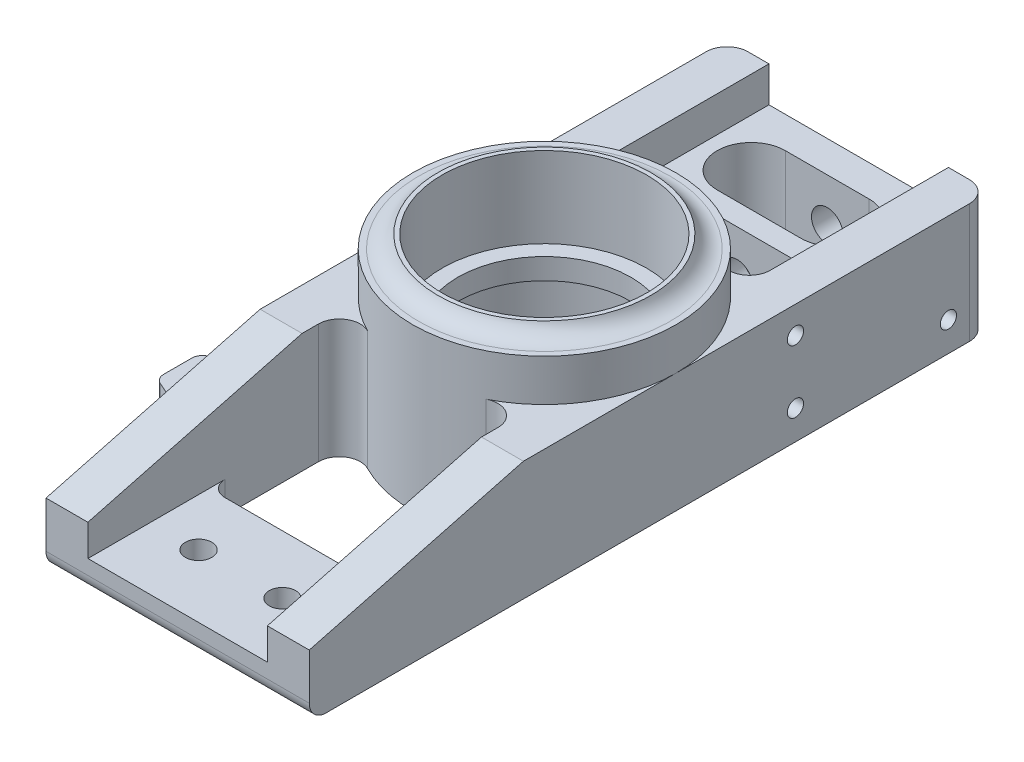
SolidWorks part; units mm, degrees
material "6061-T6 (SS)"
ref_plane "X-Y Datum" through (0, 0, 0) normal (0, 0, 1) x (1, 0, 0)
ref_plane "X-Z Datum" through (0, 0, 0) normal (0, 1, 0) x (1, 0, 0)
ref_plane "Y-Z Datum" through (0, 0, 0) normal (1, 0, 0) x (0, 0, -1)
sketch3d "KPI Sketch"
  line L0 (0, 0, 0) -> (0, 0, 50000) construction
  line L1 (0, 0, 0) -> (0, -50000, 0) construction
  line L2 (0, 0, 0) -> (-50000, 0, 0) construction
  line L3 (0, 15.9209, 92.075) -> (0, -42.747, -247.2184) construction
  line L4 (0, -10.9799, -63.5) -> (-66.3575, -10.9799, -63.5) construction
  line L5 (-66.3575, -10.9799, -63.5) -> (-66.3575, -0.8199, -63.5) construction
  line L6 (-66.3575, -0.8199, -63.5) -> (0, -10.9799, -63.5) construction
  line L7 (-66.3575, -0.8199, -52.3875) -> (-66.3575, -0.8199, -74.6125) construction
  line L8 (0, 15.9209, 92.075) -> (0, 15.9209, -75.3861) construction
  line L9 (0, -13.0351, -75.3861) -> (0, 15.9209, -75.3861) construction
  line L10 (0, -10.9799, -63.5) -> (66.3575, -10.9799, -63.5) construction
  line L11 (66.3575, -10.9799, -63.5) -> (66.3575, -0.8199, -63.5) construction
  line L12 (66.3575, -0.8199, -63.5) -> (0, -10.9799, -63.5) construction
  line L13 (66.3575, -0.8199, -63.5) -> (66.3575, -0.8199, -52.3875) construction
  line L16 (66.3575, -0.8199, -63.5) -> (66.3575, -0.8199, -74.6125) construction
  circle A0 centre (0, 0, 0) radius 127 construction
  point P11 (0, -13.0351, -75.3861)
  point P17 (-66.3575, -0.8199, -63.5)
  point P18 (0, 0, 0)
  point P19 (-66.3575, -0.8199, -63.5)
  point P22 (0, 127, 0)
  dimension "D5" = 92.075
  dimension "D8" = 254
  dimension "TOE Z" = 63.5
  dimension "D1" = 10.16
  dimension "D4" = 67.1308
  dimension "D6" = 22.225
  dimension "D2" = 169.9461
  dimension "D3" = 28.956
  dimension "D7" = 66.3575
  dimension "D9" = 66.3575
  dimension "D10" = 10.16
  dimension "D11" = 11.1125
  dimension "D12" = 11.1125
ref_axis "Wheel Spin Axis" through (0, -55.5512, 0) along (0, 1, 0)
sketch "Bearing Sketch" plane through (0, 0, 0) normal (1, 0, 0) x (0, 0, -1)
  line L11 (0, 0) -> (0, -50000) construction
  line L17 (-30.9994, -25.0922) -> (-39.8894, -25.0922)
  line L23 (-30.9994, -3.175) -> (-26.2369, -3.175)
  line L24 (55.1739, 0) -> (-55.1739, 0) construction
  line L26 (-30.9994, -3.175) -> (-30.9994, -25.0922)
  line L27 (-30.9994, 27.6332) -> (-30.9994, 3.175)
  line L28 (-30.9994, 3.175) -> (-26.2369, 3.175)
  line L29 (-26.2369, 3.175) -> (-26.2369, -3.175)
  line L31 (0, 0) -> (-50000, 0) construction
  line L33 (-30.9994, 27.6332) -> (-32.2694, 27.6332)
  line L34 (-32.2694, 27.6332) -> (-32.2694, 23.7622)
  line L35 (-32.2694, 23.7622) -> (-39.8894, 23.7622)
  line L36 (-39.8894, 23.7622) -> (-39.8894, -25.0922)
  point P3 (-26.2369, 0)
  dimension "D2" = 6.35
  dimension "D1" = 21.9172
  dimension "D4" = 24.4582
  dimension "D3" = 52.4739
  dimension "D6" = 61.9989
  dimension "D5" = 79.7789
  dimension "D7" = 64.5389
  dimension "D8" = 48.8544
revolve "Bearing Dimensions" add sketch "Bearing Sketch" angle 360 about axis through (0, -55.5512, 0) along (0, 1, 0)
sketch "UBJ Material Sketch" plane through (0, -25.0922, 0) normal (0, 1, 0) x (1, 0, 0)
  line L1 (39.8894, -46.2394) -> (-39.8894, -46.2394)
  line L3 (0, 0) -> (-50000, 0) construction
  line L4 (0, 0) -> (0, -50000) construction
  line L5 (39.8894, 0) -> (39.8894, -46.2394)
  line L7 (-39.8894, 0) -> (-39.8894, -46.2394)
  circle A0 centre (0, 0) radius 39.8894 construction
  circle A1 centre (0, 0) radius 39.8894 construction
  arc A2 (-39.8894, 0) -> (39.8894, 0) centre (0, 0) ccw
  point P5 (0, -46.2394)
  point P15 (0, -39.8894)
  dimension "D1" = 6.35
extrude "UBJ Material" add sketch "UBJ Material Sketch" along normal offset from surface (36.1544 mm away) 12.7 up to face at (0, 23.7622, -39.8894)
sketch "Sketch58" plane through (39.8894, 0, 0) normal (1, 0, 0) x (0, 0, -1)
  line L0 (0, 0) -> (-50000, 0) construction
  line L5 (0, 0) -> (0, 50000) construction
  line L14 (-46.2394, 11.0622) -> (-111.125, -6.0422)
  line L16 (-111.125, -6.0422) -> (-111.125, -25.0922)
  line L17 (-111.125, -25.0922) -> (-62.9981, -25.0922)
  line L18 (-62.9981, -25.0922) -> (-46.2394, -25.0922)
  line L19 (-46.2394, -25.0922) -> (-46.2394, 11.0622)
  line L22 (-46.2394, -25.0922) -> (0, -25.0922) construction
  point P27 (-111.125, -15.5672)
  dimension "D1" = 19.05
  dimension "D2" = 64.8856
extrude "Boss-Extrude6" add sketch "Sketch58" against normal up to surface (79.7789 mm away) contours L16 L17 L18 L19 L14 up to face at (-39.8894, -7.015, 23.1197)
sketch "Sketch9" plane through (0, -25.0922, 0) normal (0, -1, 0) x (1, 0, 0)
  line L3 (-39.8894, 0) -> (-39.8894, 111.125) construction
  line L4 (-39.8894, 0) -> (-39.8894, 111.125) construction
  line L5 (0, 0) -> (-50000, 0) construction
  line L7 (-27.1894, 29.1874) -> (-27.1894, 74.3672)
  line L12 (27.1894, 74.3672) -> (-27.1894, 74.3672)
  line L13 (27.1894, 74.3672) -> (27.1894, 29.1874)
  line L17 (39.8894, 111.125) -> (39.8894, 0) construction
  line L21 (39.8894, 111.125) -> (39.8894, 0) construction
  arc A2 (39.8894, 0) -> (-39.8894, 0) centre (0, 0) ccw construction
  arc A3 (27.1894, 29.1874) -> (-27.1894, 29.1874) centre (0, 0) ccw
  dimension "D1" = 12.7
  dimension "D2" = 12.7
extrude "UBJ Cross Member" cut sketch "Sketch9" against normal through all contours A3 L13 L12 L7 region at (0, -25.0922, 55.3249)
ref_plane "Plane1" through (0, 3.6475, 0) normal (0, -1, 0) x (-1, 0, 0)
sketch "Sketch10" plane through (0, 3.6475, -1.6553) normal (0, 1, 0) x (1, 0, 0)
  line L9 (27.1894, -70.1197) -> (-27.1894, -70.1197)
  line L10 (27.1894, -70.1197) -> (27.1894, -114.5697)
  line L11 (27.1894, -114.5697) -> (-27.1894, -114.5697)
  line L12 (-27.1894, -70.1197) -> (-27.1894, -114.5697)
  line L13 (27.1894, -47.8947) -> (27.1894, -76.0225) construction
  dimension "D1" = 44.45
extrude "UBJ Mass Removal" cut sketch "Sketch10" against normal offset from surface (19.2146 mm away) 9.525 up to face at (0, -25.0922, 45.5901)
fillet "Fillet43" radius 4.7625 2 edges at (-27.1894, -20.3297, 74.3672) (27.1894, -20.3297, 74.3672)
fillet "Fillet26" radius 6.35 2 edges at (-27.1894, -7.015, 29.1874) (27.1894, -7.015, 29.1874)
fillet "Fillet45" radius 5.08 1 edges at (0, -25.0922, 111.125)
sketch "Sketch4" plane through (0, -25.0922, 0) normal (0, -1, 0) x (1, 0, 0)
  line L1 (-39.8894, -95.25) -> (39.8894, -95.25)
  line L3 (39.8894, 0) -> (39.8894, -95.25)
  line L4 (10.3505, 0) -> (-10.3505, 0) construction
  line L5 (0, 0) -> (0, 50000) construction
  line L7 (-39.8894, 0) -> (-39.8894, -82.55)
  line L9 (-39.8894, -95.25) -> (-39.8894, -82.55)
  arc A0 (-39.8894, 0) -> (39.8894, 0) centre (0, 0) ccw construction
  arc A1 (-39.8894, 0) -> (39.8894, 0) centre (0, 0) ccw
  point P3 (0, 0)
  dimension "D1" = 95.25
  dimension "D4" = 82.55
extrude "LBJ Material" add sketch "Sketch4" against normal offset from surface (36.1544 mm away) 12.7 up to face at (0, 23.7622, -39.8894)
sketch "Sketch7" plane through (0, -25.0922, 0) normal (0, -1, 0) x (1, 0, 0)
  line L1 (-27.1894, -58.42) -> (27.1894, -58.42)
  line L3 (0, 0) -> (50000, 0) construction
  line L4 (27.1894, -29.1874) -> (27.1894, -58.42)
  line L6 (0, 0) -> (0, 50000) construction
  line L8 (39.8894, 0) -> (39.8894, -95.25) construction
  line L9 (-27.1894, -58.42) -> (-27.1894, -29.1874)
  line L11 (-39.8894, -95.25) -> (-39.8894, 0) construction
  arc A4 (-39.8894, 0) -> (39.8894, 0) centre (0, 0) ccw construction
  arc A5 (-39.8894, 0) -> (39.8894, 0) centre (0, 0) ccw
  dimension "D1" = 12.7
  dimension "D2" = 12.7
  dimension "D3" = 58.42
extrude "Cross Members" cut sketch "Sketch7" against normal up to surface (48.8544 mm away) contours L1 region at (0, -25.0922, -47.258) up to face at (0, 23.7622, -39.8894)
sketch "Sketch62" plane through (0, 0, -95.25) normal (0, 0, -1) x (-1, 0, 0)
  line L1 (-27.1894, 0.3078) -> (27.1894, 0.3078)
  line L2 (-27.1894, 0.3078) -> (-27.1894, 11.0622)
  line L3 (-27.1894, 11.0622) -> (27.1894, 11.0622)
  line L4 (27.1894, 0.3078) -> (27.1894, 11.0622)
  line L5 (-39.8894, 11.0622) -> (-39.8894, -25.0922) construction
  dimension "D1" = 12.7
extrude "Cut-Extrude1" cut sketch "Sketch62" against normal blind 44.45
sketch "Sketch5" plane through (0, -25.0922, 0) normal (0, -1, 0) x (1, 0, 0)
  line L0 (0, 0) -> (50000, 0) construction
  line L1 (0, 0) -> (0, 50000) construction
  line L2 (12.7, -75.3861) -> (-12.7, -75.3861) construction
  line L3 (12.7, -85.7112) -> (-12.7, -85.7112)
  line L4 (12.7, -65.061) -> (-12.7, -65.061)
  arc A0 (12.7, -85.7112) -> (12.7, -65.061) centre (12.7, -75.3861) ccw
  arc A1 (-12.7, -65.061) -> (-12.7, -85.7112) centre (-12.7, -75.3861) ccw
  point P8 (0, -75.3861)
  dimension "D2" = 10.3251
  dimension "D1" = 12.7
extrude "LBJ Opening" cut sketch "Sketch5" against normal up to surface (25.4 mm away) up to face at (0, 0.3078, -76.835)
fillet "LBJ Outside" radius 6.35 2 edges at (39.8894, -7.015, -95.25) (-39.8894, -7.015, -95.25)
fillet "LBJ Ramp" radius 6.35 4 edges at (-27.1894, -12.3922, -58.42) (27.1894, -12.3922, -58.42) (-27.1894, -7.015, -29.1874) (27.1894, -7.015, -29.1874)
fillet "BH Lip" radius 6.35 1 edges at (0, 23.7622, -32.2694)
hole_wizard "Ø8.0mm Dowel Hole1" positions "Sketch25" profile "Sketch26" hole size "Ø8.0" standard "ANSI Metric"
sketch "Sketch25" plane through (0, -15.5672, 0) normal (0, 1, 0) x (1, 0, 0)
  line L0 (12.7, -92.075) -> (-12.7, -92.075) construction
  line L2 (0, 200000) -> (0, -250000) construction
  line L5 (0, 0) -> (0, -50000) construction
  line L6 (0, 0) -> (-50000, 0) construction
  point P0 (12.7, -92.075)
  point P2 (-12.7, -92.075)
  dimension "D1" = 12.7
  dimension "D2" = 12.7
  dimension "D3" = 92.075
sketch "Sketch26" plane through (12.7, -15.5672, 92.075) normal (1, 0, 0) x (0, 0, 1)
  line L0 (0, 0) -> (0, 16.002)
  line L1 (0, 16.002) -> (4, 13.5986)
  line L2 (4, 13.5986) -> (4, 0)
  line L5 (4, 0) -> (0, 0)
  line L10 (0, 16.002) -> (-4, 13.5986) construction
  line L11 (0, -6.35) -> (0, 107.95) construction
  dimension "Hole Dia." = 8
  dimension "Hole Depth" = 16.002
  dimension "Drill Angle" = 118
sketch "Sketch30" plane through (0, -25.0922, 0) normal (0, -1, 0) x (1, 0, 0)
  line L1 (0, 0) -> (-50000, 0) construction
  line L2 (0, 0) -> (0, 50000) construction
  line L6 (-39.8894, -31.4891) -> (-39.8894, -65.3856)
  line L18 (-63.4528, -56.9861) -> (-53.5589, -60.5129)
  line L19 (-63.4528, -43.0161) -> (-39.8894, -31.4891)
  line L20 (-63.4197, 41.3533) -> (-39.8894, 30.3086)
  line L21 (-63.4197, 54.04) -> (-39.8894, 64.2936)
  line L22 (-39.8894, 64.2936) -> (-39.8894, 30.3086)
  line L23 (-53.5589, -60.5129) -> (-39.8894, -65.3856)
  line L24 (-63.4528, -43.0161) -> (-63.4528, -56.9861)
  line L25 (-63.4197, 54.04) -> (-63.4197, 41.3533)
  line L27 (-39.8894, -88.9) -> (-39.8894, 0) construction
  line L28 (-39.8894, 46.2394) -> (-39.8894, 0) construction
  line L29 (-39.8894, -88.9) -> (-39.8894, 106.045) construction
  circle A2 centre (-55.6468, -48.8308) radius 3 construction
  circle A3 centre (-55.6468, 47.1692) radius 3 construction
  point P50 (-55.6468, -48.8308)
  point P51 (-55.6468, 47.1692)
  dimension "D1" = 96
  dimension "D2" = 55.6468
  dimension "D3" = 6
extrude "Boss-Extrude1" add sketch "Sketch30" against normal blind 10.16
fillet "Fillet33" radius 3.175 4 edges at (-63.4197, -20.0122, 41.3533) (-63.4197, -20.0122, 54.04) (-63.4528, -20.0122, -43.0161) (-63.4528, -20.0122, -56.9861)
fillet "Fillet34" radius 6.35 4 edges at (-39.8894, -20.0122, -65.3856) (-39.8894, -20.0122, -31.4891) (-39.8894, -20.0122, 30.3086) (-39.8894, -20.0122, 64.2936)
hole_wizard "CBORE for M8 Hex Head Bolt1" positions "Sketch32" profile "Sketch33" counterbore size "M8" standard "ANSI Metric"
sketch "Sketch32" plane through (0, -25.0922, 0) normal (0, 1, 0) x (1, 0, 0)
  point P9 (-55.6468, -47.1692)
  point P12 (-55.6468, 48.8308)
sketch "Sketch33" plane through (-55.6468, -25.0922, 47.1692) normal (1, 0, 0) x (0, 0, -1)
  line L0 (0, 0) -> (0, 16.002)
  line L1 (0, 16.002) -> (4.2, 13.4784)
  line L2 (4.2, 13.4784) -> (4.2, 5)
  line L3 (4.2, 5) -> (6.75, 5)
  line L4 (6.75, 5) -> (6.75, 0)
  line L5 (6.75, 0) -> (0, 0)
  line L10 (0, 16.002) -> (-4.2, 13.4784) construction
  line L11 (0, -6.35) -> (0, 107.95) construction
  dimension "Hole Dia." = 8.4
  dimension "Hole Depth" = 16.002
  dimension "C'Bore Dia." = 13.5
  dimension "C'Bore Depth" = 5
  dimension "Drill Angle" = 118
chamfer "Chamfer1" [suppressed] distance 1.5875 angle 45
sketch "Sketch34" plane through (0, -25.0922, 0) normal (0, -1, 0) x (1, 0, 0)
  circle A0 centre (0, 0) radius 50.4825 construction
  circle A1 centre (50.4825, 0) radius 5.9531 construction
  point P3 (50.4825, 0)
  dimension "D1" = 100.965
  dimension "D3" = 11.9062
sketch "Sketch37" plane through (0, -25.0922, 0) normal (0, -1, 0) x (1, 0, 0)
  line L1 (-39.8894, -88.9) -> (-39.8894, 0) construction
  line L5 (-39.8894, -11.1125) -> (-58.9394, -11.1125)
  line L10 (-39.8894, -11.1125) -> (-39.8894, 11.1125)
  line L12 (-39.8894, 11.1125) -> (-58.9394, 11.1125)
  line L13 (-58.9394, -11.1125) -> (-58.9394, 11.1125)
  line L15 (200000, 0) -> (-250000, 0) construction
  point P7 (-58.9394, 0)
  dimension "D2" = 19.05
  dimension "D3" = 22.225
extrude "Speed Sensor Extrude" add sketch "Sketch37" against normal blind 7.716
hole_wizard "3/8 (0.375) Diameter Hole2" positions "Sketch50" profile "Sketch51" hole size "3/8" standard "ANSI Inch"
sketch "Sketch50" plane through (0, 0, -95.25) normal (0, 0, -1) x (-1, 0, 0)
  point P0 (0, -13.0351)
sketch "Sketch51" plane through (0, -13.0351, -95.25) normal (1, 0, 0) x (0, 1, 0)
  line L0 (0, 0) -> (0, 39.6916)
  line L1 (0, 39.6916) -> (4.7625, 36.83)
  line L2 (4.7625, 36.83) -> (4.7625, 0)
  line L5 (4.7625, 0) -> (0, 0)
  line L10 (0, 39.6916) -> (-4.7625, 36.83) construction
  line L11 (0, -6.35) -> (0, 107.95) construction
  dimension "Hole Dia." = 9.525
  dimension "Hole Depth" = 36.83
  dimension "Drill Angle" = 118
fillet "Fillet47" radius 6.35 4 edges at (-39.8894, -21.2341, 11.1125) (-58.9394, -21.2341, 11.1125) (-39.8894, -21.2341, -11.1125) (-58.9394, -21.2341, -11.1125)
hole_wizard "15/32 (0.46875) Diameter Hole1" positions "Sketch35" profile "Sketch36" hole size "15/32" standard "ANSI Inch"
sketch "Sketch35" plane through (0, -17.3761, 0) normal (0, 1, 0) x (1, 0, 0)
  line L0 (200000, 0) -> (-250000, 0) construction
  circle A0 centre (0, 0) radius 50.4825 construction
  point P0 (-50.4825, 0)
sketch "Sketch36" plane through (-50.4825, -17.3761, 0) normal (1, 0, 0) x (0, 0, 1)
  line L0 (0, 0) -> (0, 16.002)
  line L1 (0, 16.002) -> (5.9531, 12.425)
  line L2 (5.9531, 12.425) -> (5.9531, 0)
  line L5 (5.9531, 0) -> (0, 0)
  line L10 (0, 16.002) -> (-5.9531, 12.425) construction
  line L11 (0, -6.35) -> (0, 107.95) construction
  dimension "Hole Dia." = 11.9062
  dimension "Hole Depth" = 16.002
  dimension "Drill Angle" = 118
fillet "Fillet49" [suppressed] radius 4.7625
sketch "Sketch59" plane through (39.8894, 0, 0) normal (-1, 0, 0) x (0, 0, 1)
  line L0 (106.045, -25.0922) -> (-88.9, -25.0922) construction
  line L1 (-95.25, 11.0622) -> (-95.25, -25.0922) construction
  point P0 (-36.195, 2.8478)
  point P1 (-36.195, -16.2022)
  point P4 (-82.55, -16.2022)
  dimension "D1" = 19.05
  dimension "D2" = 46.355
  dimension "D3" = 8.89
  dimension "D4" = 12.7
hole_wizard "#10 (0.1935) Diameter Hole1" positions "Sketch60" profile "Sketch61" hole size "#10" standard "ANSI Inch"
sketch "Sketch60" plane through (39.8894, 0, 0) normal (-1, 0, 0) x (0, 0, 1)
  point P0 (-82.55, -16.2022)
  point P6 (-36.195, 2.8478)
  point P9 (-36.195, -16.2022)
sketch "Sketch61" plane through (39.8894, -16.2022, -82.55) normal (0, 1, 0) x (0, 0, -1)
  line L0 (0, 0) -> (0, 11.1125)
  line L1 (0, 11.1125) -> (2.4574, 9.6359)
  line L2 (2.4574, 9.6359) -> (2.4574, 0)
  line L5 (2.4574, 0) -> (0, 0)
  line L10 (0, 11.1125) -> (-2.4575, 9.6359) construction
  line L11 (0, -6.35) -> (0, 107.95) construction
  dimension "Hole Dia." = 4.9149
  dimension "Hole Depth" = 11.1125
  dimension "Drill Angle" = 118
equation "\"KPI\"= 9.56"
equation "\"TOE alng x\"= 77.1mm"
equation "\"x dtm to toe\"= 36.4mm"
equation "\"XY to toe\"= 30.7mm"
equation "\"XZ to LBJ\"= 22.08mm"
equation "\"XY to LBJ\"= 3.2"
equation "\"XY to UBJ\"=3.625"
equation "\"Bearing Inner Bore\"= 1.25'RADIUS"
equation "\"Bearing Outer Bore\"= 2.4409'RADIUS"
equation "\"Bearing Thickness\"= .7150"
equation "\"D1@Bearing Sketch\"=\"Bearing Thickness\" +.25-0.09712-0.005"
equation "\"D4@Bearing Sketch\"=\"Bearing Thickness\" +.2625-0.06458+.05"
equation "\"D3@Bearing Sketch\"=\"Bearing Outer Bore\" - .375"
equation "\"D6@Bearing Sketch\" = \"Bearing Outer Bore\""
equation "\"D5@Bearing Sketch\" = \"Bearing Outer Bore\" + 2 * .35"
equation "\"D7@Bearing Sketch\" = \"Bearing Outer Bore\" + .1"
equation "\"D8@Bearing Sketch\"=\"Bearing Thickness\" * 2 + 0.225 + 0.2684"
equation "\"D1@Sketch4\"=\"XY to LBJ\" + .25+.3"
equation "\"D1Sketch21\"= \"XY to UBJ\" + 0.375"
equation "\"D3@Sketch25\"=\"XY to UBJ\""
equation "\"D5@KPI Sketch\"=\"XY to UBJ\""
